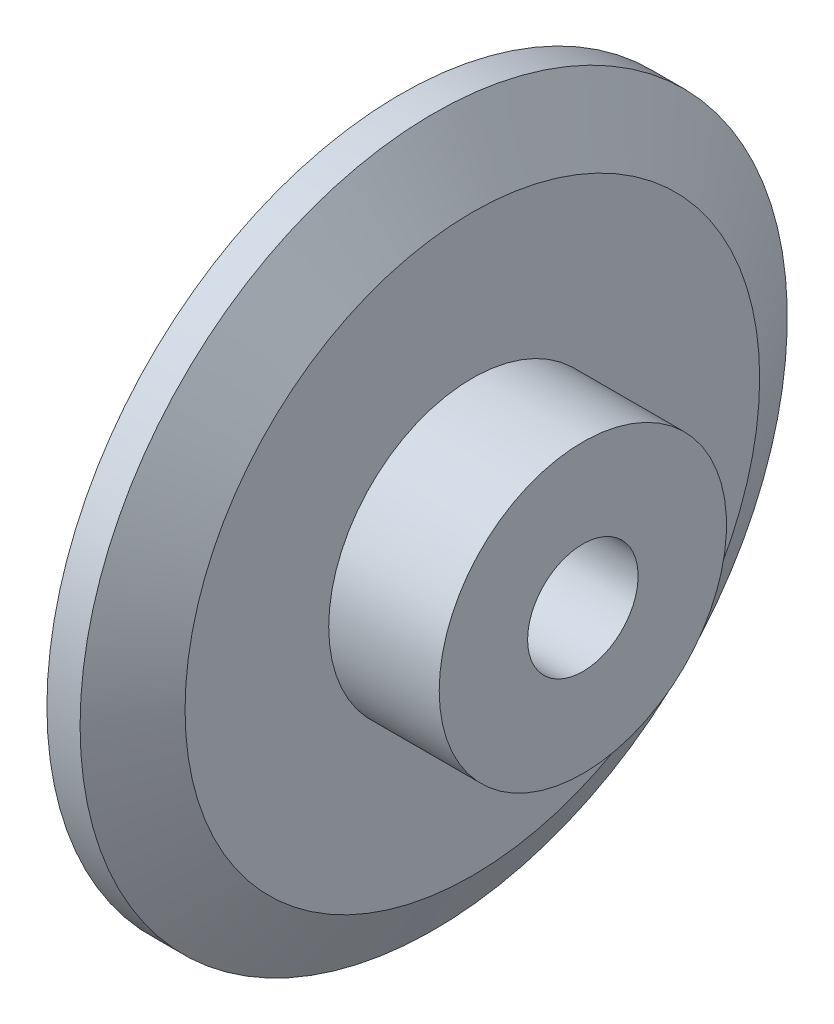
SolidWorks part; units mm, degrees
ref_plane "Plan de face" through (0, 0, 0) normal (0, 0, 1) x (1, 0, 0)
ref_plane "Plan de dessus" through (0, 0, 0) normal (0, 1, 0) x (1, 0, 0)
ref_plane "Plan de droite" through (0, 0, 0) normal (1, 0, 0) x (0, 0, -1)
sketch "Esquisse1" plane through (0, 0, 0) normal (0, 0, 1) x (1, 0, 0)
  line L0 (-14.53, 0) -> (21.3018, 0) construction
  line L1 (-2.5, 2.5) -> (7.5, 2.5)
  line L2 (7.5, 2.5) -> (7.5, 6.5)
  line L3 (7.5, 6.5) -> (2.5, 6.5)
  line L4 (2.5, 6.5) -> (2.5, 13)
  line L5 (2.5, 13) -> (0.75, 16)
  line L6 (0.75, 16) -> (-0.75, 16)
  line L7 (-0.75, 16) -> (-2.5, 13)
  line L8 (-2.5, 13) -> (-2.5, 2.5)
  line L9 (0, 0) -> (0, 37.6755) construction
  dimension "D1" = 5
  dimension "D2" = 32
  dimension "D3" = 4
  dimension "D4" = 5
  dimension "D5" = 1.5
  dimension "D6" = 3
  dimension "D7" = 5
  dimension "D8" = 10
revolve "Révolution1" add sketch "Esquisse1" angle 360 about L0
